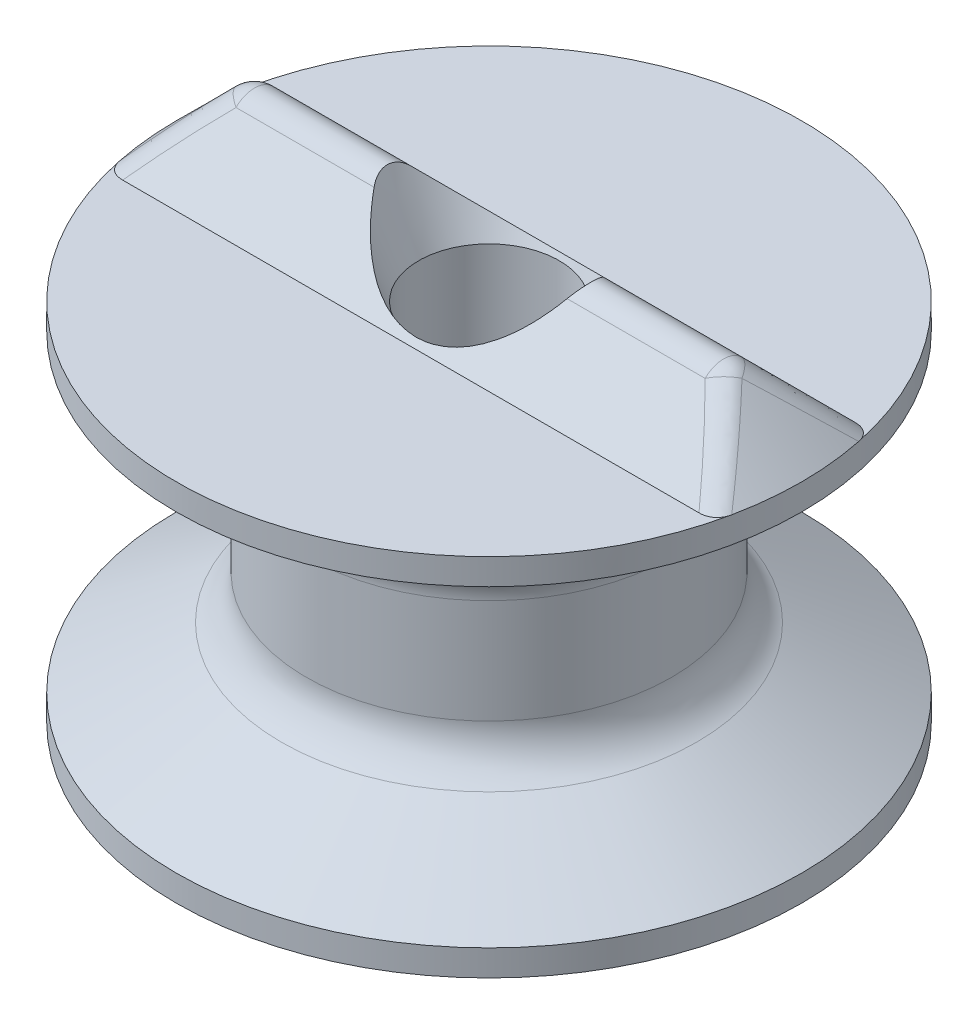
SolidWorks part; units mm, degrees
ref_plane "Front Plane" through (0, 0, 0) normal (0, 0, 1) x (1, 0, 0)
ref_plane "Top Plane" through (0, 0, 0) normal (0, 1, 0) x (1, 0, 0)
ref_plane "Right Plane" through (0, 0, 0) normal (1, 0, 0) x (0, 0, -1)
sketch "Sketch1" plane through (0, 0, 0) normal (0, 0, 1) x (1, 0, 0)
  line L0 (1.35, 0) -> (1.35, 7)
  line L1 (1.35, 7) -> (6, 7)
  line L2 (6, 6.5) -> (3.9821, 5.3349)
  line L3 (3.5, 4.5) -> (3.5, 2.5)
  line L4 (3.9821, 1.6651) -> (6, 0.5)
  line L5 (6, 0) -> (1.35, 0)
  line L6 (6, 7) -> (6, 6.5)
  line L7 (6, 0) -> (6, 0.5)
  line L9 (0, -1000) -> (0, 49000) construction
  arc A0 (3.9821, 5.3349) -> (3.5, 4.5) centre (4.4641, 4.5) ccw
  arc A1 (3.5, 2.5) -> (3.9821, 1.6651) centre (4.4641, 2.5) ccw
  dimension "D1" = 2
  dimension "D2" = 30
  dimension "D3" = 30
  dimension "D4" = 0.5
  dimension "D5" = 7
  dimension "D6" = 12
  dimension "D7" = 7
  dimension "D8" = 2.7
revolve "Revolve1" add sketch "Sketch1" angle 360 about L9
sketch "Sketch2" plane through (0, 0, 0) normal (1, 0, 0) x (0, 0, -1)
  line L0 (1.5, 7) -> (-1.5, 7)
  line L1 (6, 7) -> (-6, 7) construction
  line L2 (-1.5, 7) -> (0, 8.5)
  line L3 (0, 8.5) -> (1.5, 7)
  point P5 (0, 7)
  dimension "D1" = 90
  dimension "D2" = 1.5
extrude "Boss-Extrude1" add sketch "Sketch2" along normal mid plane 20
sketch "Sketch3" plane through (0, 0, 0) normal (0, 0, 1) x (1, 0, 0)
  line L0 (-6, 7) -> (-4.5, 8.5)
  line L1 (10, 8.5) -> (-10, 8.5) construction
  line L2 (-4.5, 8.5) -> (-12.2994, 8.5)
  line L3 (-2.0495, 8.5) -> (-1.35, 7)
  line L5 (-12.2994, 8.5) -> (-12.2994, 7)
  line L6 (5.8095, 7) -> (-5.8095, 7) construction
  line L7 (-12.2994, 7) -> (-6, 7)
  line L8 (0, 7) -> (-1.35, 7)
  line L9 (5.8095, 7) -> (-5.8095, 7) construction
  line L10 (-2.0495, 8.5) -> (0, 8.5)
  line L11 (0, 8.5) -> (0, 7)
  point P6 (-1.35, 0)
  dimension "D1" = 65
  dimension "D2" = 45
revolve "Cut-Revolve1" cut sketch "Sketch3" angle 360 about L11
fillet "Fillet1" radius 0.5 6 edges at (3.2747, 8.5, 0) (-3.2747, 8.5, 0)
